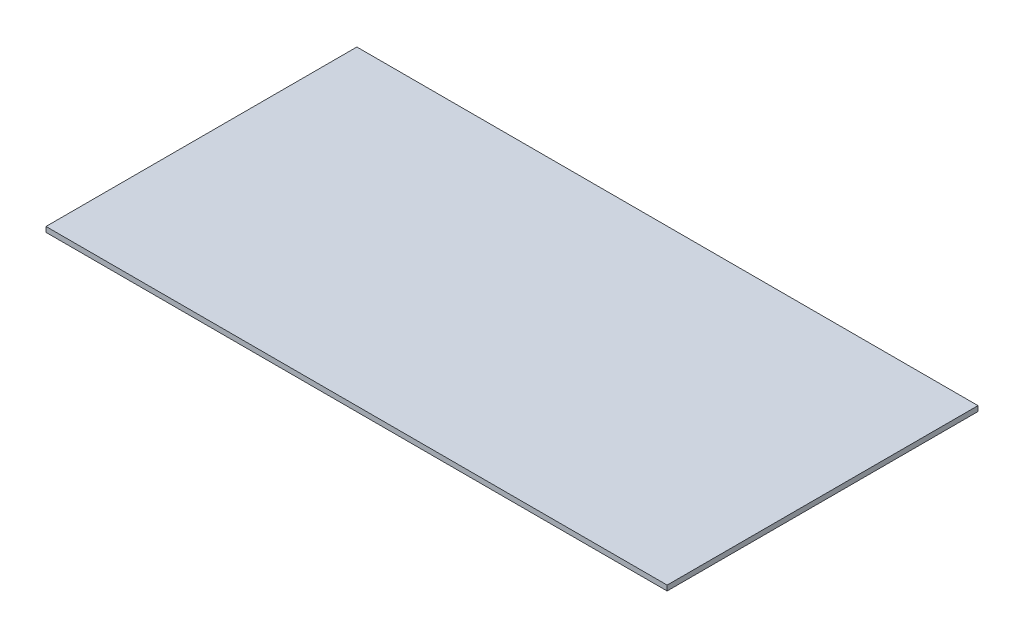
SolidWorks part; units mm, degrees
ref_plane "Front Plane" through (0, 0, 0) normal (0, 0, 1) x (1, 0, 0)
ref_plane "Top Plane" through (0, 0, 0) normal (0, 1, 0) x (1, 0, 0)
ref_plane "Right Plane" through (0, 0, 0) normal (1, 0, 0) x (0, 0, -1)
sketch "Sketch1" plane through (0, 0, 0) normal (0, 1, 0) x (1, 0, 0)
  line L1 (-41.2218, 0) -> (320.459, 0)
  line L2 (-41.2218, 0) -> (-41.2218, 181)
  line L3 (-41.2218, 181) -> (320.459, 181)
  line L4 (320.459, 0) -> (320.459, 181)
  point P5 (0, 181)
  point P6 (-41.2218, 181)
  dimension "D1" = 181
extrude "Boss-Extrude1" add sketch "Sketch1" along normal blind 3
